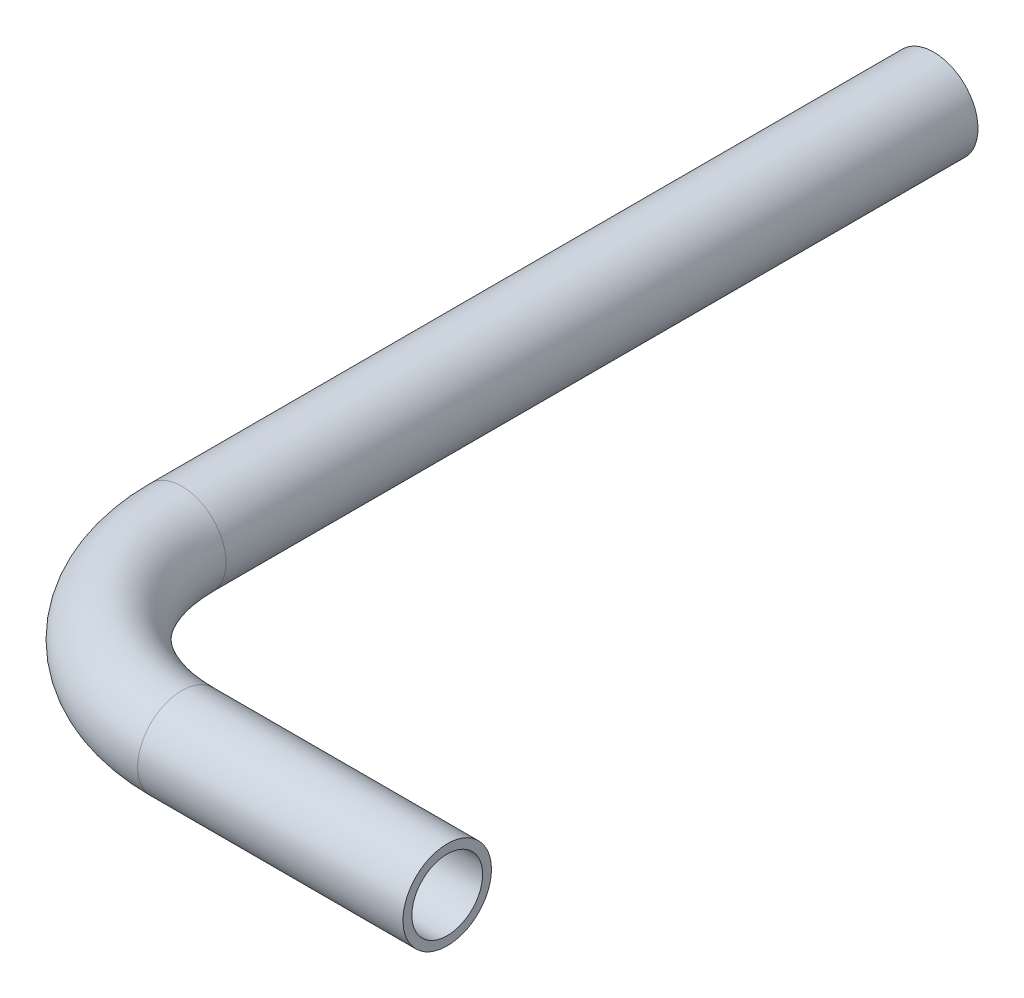
SolidWorks part; units mm, degrees
material "Chrome Stainless Steel"
ref_plane "Front" through (0, 0, 0) normal (0, 0, 1) x (1, 0, 0)
ref_plane "Top" through (0, 0, 0) normal (0, 1, 0) x (1, 0, 0)
ref_plane "Right" through (0, 0, 0) normal (1, 0, 0) x (0, 0, -1)
ref_axis "Axis1" through (0, 0, 55) along (0, 0, -1)
sketch "Sketch1" plane through (0, 0, 0) normal (0, 1, 0) x (1, 0, 0)
  line L0 (0, 0) -> (0, -107.95)
  line L1 (25.4, -133.35) -> (63.5, -133.35)
  arc A0 (25.4, -133.35) -> (0, -107.95) centre (25.4, -107.95) cw
  point P6 (0, -133.35)
  dimension "D3" = 25.4
  dimension "D1" = 133.35
  dimension "D2" = 63.5
sketch "Sketch2" plane through (0, 0, 0) normal (0, 0, 1) x (1, 0, 0)
  circle A0 centre (0, 0) radius 6.35
  dimension "D1" = 12.7
sweep "Sweep-Thin1" add profiles "Sketch2" path "Sketch1" parameters "D1"=1.27
